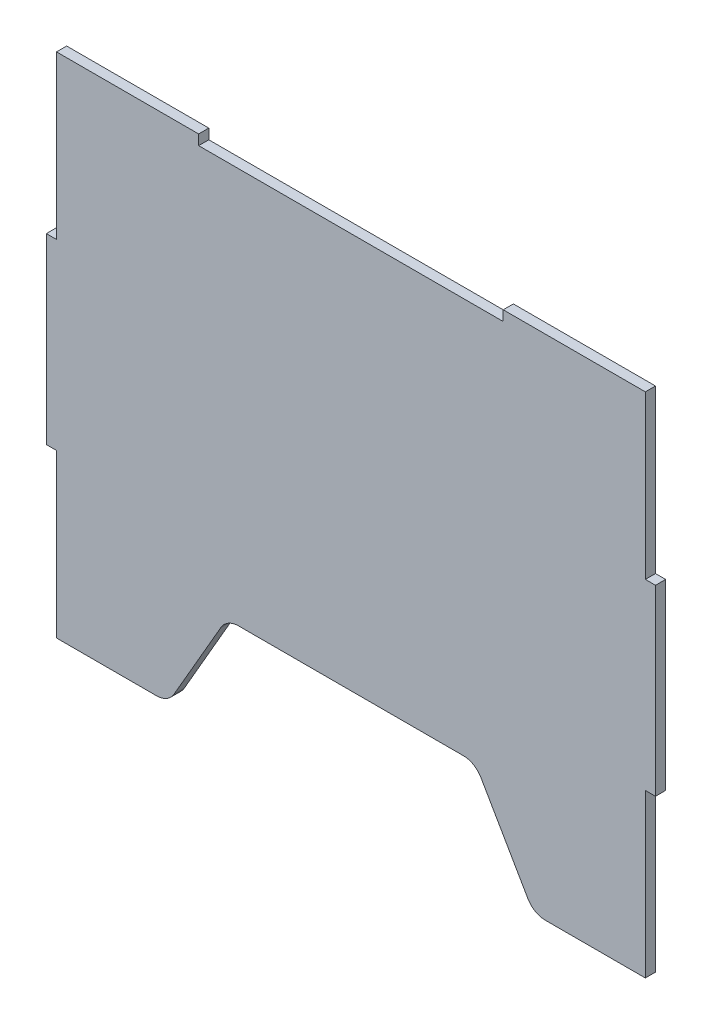
SolidWorks part; units mm, degrees
ref_plane "Ebene vorne" through (0, 0, 0) normal (0, 0, 1) x (1, 0, 0)
ref_plane "Ebene oben" through (0, 0, 0) normal (0, 1, 0) x (1, 0, 0)
ref_plane "Ebene rechts" through (0, 0, 0) normal (1, 0, 0) x (0, 0, -1)
sketch "Skizze1" plane through (0, 0, 0) normal (0, 0, 1) x (1, 0, 0)
  line L1 (-150, 125) -> (150, 125)
  line L2 (-150, 125) -> (-150, -125)
  line L3 (-150, -125) -> (150, -125)
  line L4 (150, 125) -> (150, -125)
  line L5 (-150, 125) -> (150, -125) construction
  line L6 (-150, -125) -> (150, 125) construction
  point P0 (0, 0)
  dimension "D1" = 250
  dimension "D2" = 300
extrude "Aufsatz-Linear austragen1" add sketch "Skizze1" along normal blind 5
sketch "Skizze2" plane through (0, 0, 5) normal (0, 0, 1) x (1, 0, 0)
  line L0 (0, 125) -> (0, -125) construction
  line L1 (150, 125) -> (-150, 125) construction
  line L2 (-150, -125) -> (150, -125) construction
  line L3 (150, -45) -> (145, -45)
  line L4 (-150, 125) -> (-145, 125)
  line L5 (-150, 125) -> (-150, 45)
  line L6 (-150, 45) -> (-145, 45)
  line L7 (-145, 125) -> (-145, 45)
  line L8 (-150, -125) -> (-145, -125)
  line L9 (-150, -125) -> (-150, -45)
  line L10 (-150, -45) -> (-145, -45)
  line L11 (-145, -125) -> (-145, -45)
  line L12 (150, -125) -> (150, -45)
  line L13 (150, -125) -> (145, -125)
  line L14 (150, 45) -> (145, 45)
  line L15 (150, 125) -> (150, 45)
  line L16 (150, 125) -> (145, 125)
  line L17 (145, -125) -> (145, -45)
  line L18 (145, 125) -> (145, 45)
  dimension "D1" = 5
  dimension "D2" = 80
extrude "Schnitt-Linear austragen1" cut sketch "Skizze2" against normal up to surface (5 mm away) up to face at (0, 0, 0)
sketch "Skizze3" plane through (0, 0, 5) normal (0, 0, 1) x (1, 0, 0)
  line L0 (0, 125) -> (0, -125) construction
  line L1 (145, 125) -> (-145, 125) construction
  line L2 (-145, -125) -> (145, -125) construction
  line L7 (75, 125) -> (-75, 125)
  line L8 (-75, 125) -> (-75, 120)
  line L9 (-75, 120) -> (75, 120)
  line L10 (75, 125) -> (75, 120)
  point P10 (0, 120)
  dimension "D1" = 150
  dimension "D2" = 5
extrude "Schnitt-Linear austragen2" cut sketch "Skizze3" against normal through all
sketch "Skizze4" plane through (0, 0, 5) normal (0, 0, 1) x (1, 0, 0)
  line L0 (0, 120) -> (0, -125) construction
  line L1 (-75, 120) -> (75, 120) construction
  line L2 (-145, -125) -> (145, -125) construction
  line L3 (90, -125) -> (-90, -125)
  line L4 (-90, -125) -> (-61.1325, -75)
  line L5 (-61.1325, -75) -> (61.1325, -75)
  line L6 (90, -125) -> (61.1325, -75)
  point P11 (0, -75)
  dimension "D1" = 50
  dimension "D2" = 180
  dimension "D3" = 60
extrude "Schnitt-Linear austragen3" cut sketch "Skizze4" against normal through all
fillet "Verrundung1" radius 10 4 edges at (-61.1325, -75, 2.5) (61.1325, -75, 2.5) (90, -125, 2.5) (-90, -125, 2.5)
